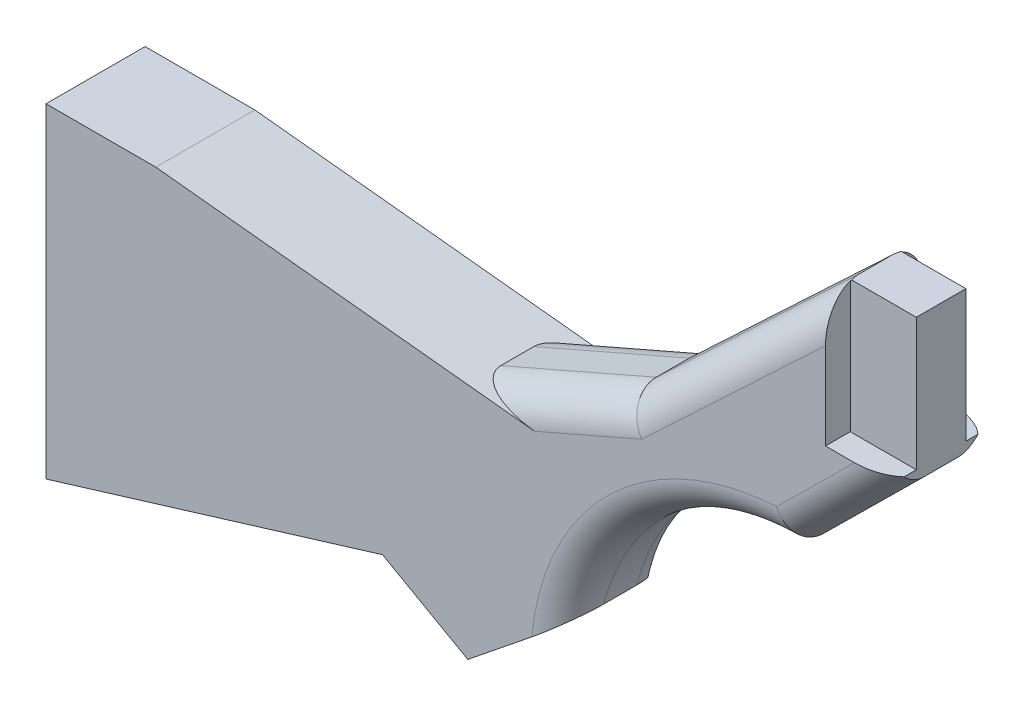
SolidWorks part; units mm, degrees
ref_plane "정면" through (0, 0, 0) normal (0, 0, 1) x (1, 0, 0)
ref_plane "윗면" through (0, 0, 0) normal (0, 1, 0) x (1, 0, 0)
ref_plane "우측면" through (0, 0, 0) normal (1, 0, 0) x (0, 0, -1)
sketch "스케치1" plane through (0, 0, 0) normal (0, 0, 1) x (1, 0, 0)
  line L0 (0, 0) -> (0, -43)
  line L2 (-20, 0) -> (-81.2267, -57.583)
  line L3 (0, 0) -> (-20, 0)
  line L4 (-20, 0) -> (-20, -40)
  line L5 (-20, -40) -> (0, -40)
  line L6 (-81.2267, -57.583) -> (-128.2946, -78.0766)
  line L7 (-128.2946, -78.0766) -> (-222.7528, -68.2719)
  line L8 (-97.1549, -125.0457) -> (-128.2946, -150.1178)
  line L9 (-128.2946, -150.1178) -> (-154.1116, -135.5753)
  line L10 (-154.1116, -135.5753) -> (-255.9997, -166.6686)
  line L11 (-255.9997, -166.6686) -> (-255.9997, -68.2719)
  line L12 (-255.9997, -68.2719) -> (-222.7528, -68.2719)
  line L13 (0, -43) -> (-30.5629, -73.1935)
  arc A0 (-30.5629, -73.1935) -> (-97.1549, -125.0457) centre (-30.5629, -141.8805) ccw
  dimension "D1" = 20
  dimension "D2" = 40
  dimension "D3" = 3
extrude "보스-돌출1" add sketch "스케치1" along normal mid plane 15 contours L4 L5 L0 L3 region at (-10, -20, 0)
extrude "보스-돌출2" add sketch "스케치1<4>" along normal mid plane 30 contours A0 L0 L5 L4 L2 L6 L7 L12 L11 L10 L9 L8 region at (-150.2601, -96.7495, 0)
sketch "스케치1<4>" plane through (0, 0, 0) normal (0, 0, 1) x (1, 0, 0) same geometry as "스케치1"
fillet "필렛1" radius 10 8 edges at (-15.2814, -58.0968, 15) (-15.2814, -58.0968, -15) (-72.7622, -87.6853, -15) (-72.7622, -87.6853, 15) (-104.7606, -67.8298, -15) (-104.7606, -67.8298, 15) (-50.6133, -28.7915, -15) (-50.6133, -28.7915, 15)
